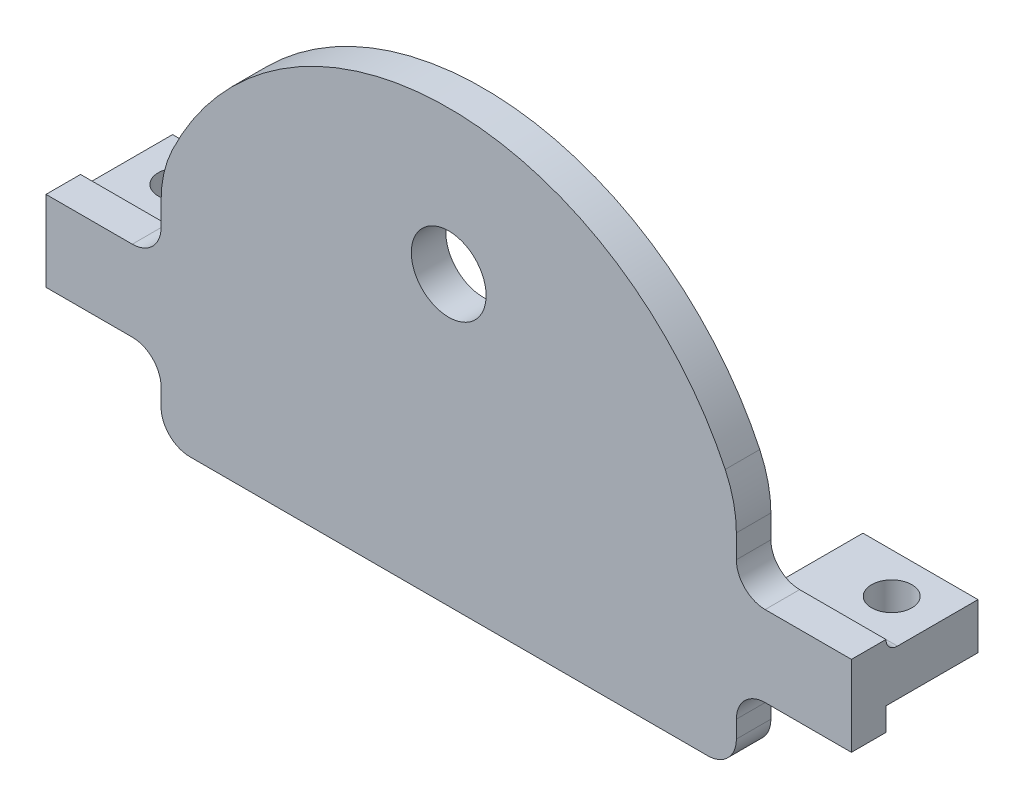
SolidWorks part; units mm, degrees
ref_plane "Front Plane" through (0, 0, 0) normal (0, 0, 1) x (1, 0, 0)
ref_plane "Top Plane" through (0, 0, 0) normal (0, 1, 0) x (1, 0, 0)
ref_plane "Right Plane" through (0, 0, 0) normal (1, 0, 0) x (0, 0, -1)
sketch "Sketch1" plane through (0, 0, 0) normal (0, 0, 1) x (1, 0, 0)
  line L1 (10, 77.5) -> (-10, 77.5)
  line L2 (10, 77.5) -> (10, -77.5)
  line L3 (10, -77.5) -> (-10, -77.5)
  line L4 (-10, 77.5) -> (-10, -77.5)
  line L5 (10, 77.5) -> (-10, -77.5) construction
  line L6 (10, -77.5) -> (-10, 77.5) construction
  point P0 (0, 0)
  dimension "D1" = 20
  dimension "D2" = 155
extrude "Boss-Extrude1" add sketch "Sketch1" along normal blind 4
sketch "Sketch2" plane through (0, 0, 4) normal (0, 0, 1) x (1, 0, 0)
  line L0 (10, -77.5) -> (10, 77.5) construction
  line L1 (-10, -77.5) -> (10, -77.5)
  line L2 (-10, -77.5) -> (-10, -73.5)
  line L3 (-10, -73.5) -> (10, -73.5)
  line L4 (10, -77.5) -> (10, -73.5)
  dimension "D1" = 4
extrude "Boss-Extrude3" add sketch "Sketch2" along normal blind 50 contours L3 L4 L1 L2
sketch "Sketch7" plane through (0, 0, 0) normal (1, 0, 0) x (0, 0, -1)
  line L0 (-29, -73.5) -> (-4, 21.5)
  line L1 (-54, -73.5) -> (-4, -73.5) construction
  line L2 (-4, -73.5) -> (-4, 77.5) construction
  dimension "D1" = 95
  dimension "D2" = 25
rib "Rib2" sketch "Sketch7" sketch "Sketch7" thickness 4 extrusion direction parallel to sketch draft on no parameters "D1"=4
sketch "Sketch8" plane through (0, 0, 4) normal (0, 0, 1) x (1, 0, 0)
  line L0 (-10, 77.5) -> (-10, -73.5) construction
  line L1 (10, 77.5) -> (-10, 77.5)
  line L2 (10, 77.5) -> (10, 74.5)
  line L3 (10, 74.5) -> (-10, 74.5)
  line L4 (-10, 77.5) -> (-10, 74.5)
  dimension "D1" = 3
extrude "Boss-Extrude4" add sketch "Sketch8" along normal blind 3.5
sketch "Sketch9" plane through (0, 0, 7.5) normal (0, 0, 1) x (1, 0, 0)
  line L1 (-35, 79.5) -> (35, 79.5)
  line L2 (-35, 79.5) -> (-35, 74.5)
  line L3 (-35, 74.5) -> (35, 74.5)
  line L4 (35, 79.5) -> (35, 74.5)
  line L5 (10, -73.5) -> (10, 74.5) construction
  line L7 (-10, 74.5) -> (10, 74.5) construction
  dimension "D1" = 70
  dimension "D2" = 25
  dimension "D3" = 5
extrude "Boss-Extrude6" add sketch "Sketch9" along normal blind 3
sketch "Sketch10" plane through (0, 0, 7.5) normal (0, 0, -1) x (-1, 0, 0)
  line L1 (35, 74.5) -> (25, 74.5)
  line L2 (35, 74.5) -> (35, 78.5)
  line L3 (35, 78.5) -> (25, 78.5)
  line L4 (25, 74.5) -> (25, 78.5)
  line L5 (-35, 74.5) -> (-25, 74.5)
  line L6 (-35, 74.5) -> (-35, 78.5)
  line L7 (-35, 78.5) -> (-25, 78.5)
  line L8 (-25, 74.5) -> (-25, 78.5)
  dimension "D1" = 10
  dimension "D2" = 4
extrude "Boss-Extrude7" add sketch "Sketch10" along normal blind 8
sketch "Sketch12" plane through (0, 78.5, 0) normal (0, 1, 0) x (1, 0, 0)
  line L1 (-35, -7.5) -> (-25, -7.5) construction
  line L2 (-35, 0.5) -> (-35, -7.5) construction
  line L3 (35, -7.5) -> (-35, -7.5) construction
  line L4 (35, 0.5) -> (35, -7.5) construction
  circle A0 centre (-31, -3) radius 1.75
  circle A1 centre (31, -3) radius 1.75
  dimension "D1" = 3.5
  dimension "D4" = 3.5
  dimension "D2" = 4.5
  dimension "D3" = 4
  dimension "D5" = 4.5
  dimension "D6" = 4
extrude "Cut-Extrude1" cut sketch "Sketch12" against normal blind 10
sketch "Sketch13" plane through (0, -77.5, 0) normal (0, -1, 0) x (1, 0, 0)
  line L1 (58.3124, -29.3972) -> (-53.0067, -29.3972)
  line L2 (58.3124, -29.3972) -> (58.3124, 70.3466)
  line L3 (58.3124, 70.3466) -> (-53.0067, 70.3466)
  line L4 (-53.0067, -29.3972) -> (-53.0067, 70.3466)
extrude "Cut-Extrude2" cut sketch "Sketch13" against normal up to surface (152 mm away) up to face at (-31, 74.5, 4.75)
sketch "Sketch14" plane through (0, 79.5, 0) normal (0, 1, 0) x (1, 0, 0)
  line L0 (35, -10.5) -> (-35, -10.5) construction
  line L1 (-25, -10.5) -> (25, -10.5)
  line L2 (-25, -10.5) -> (-25, -7.5)
  line L3 (-25, -7.5) -> (25, -7.5)
  line L4 (25, -10.5) -> (25, -7.5)
  line L5 (-25, 0.5) -> (-25, -7.5) construction
  line L6 (25, 0.5) -> (25, -7.5) construction
extrude "Boss-Extrude8" add sketch "Sketch14" along normal blind 6.5
ref_plane "Plane1" through (0, 76, 0) normal (0, -1, 0) x (-1, 0, 0)
mirror "Mirror1" about plane through (0, 76, 0) normal (0, -1, 0) of "Boss-Extrude6", "Boss-Extrude8"
fillet "Fillet1" radius 1 7 edges at (30, 78.5, 7.5) (-30, 78.5, 7.5) (10, 76, 7.5) (-10, 76, 7.5) (0, 77.5, 7.5) (25, 76.5, 7.5) (-25, 76.5, 7.5)
fillet "Fillet2" radius 2.5 6 edges at (-25, 66, 9) (25, 66, 9) (-25, 72.5, 9) (-25, 79.5, 9) (25, 72.5, 9) (25, 79.5, 9)
sketch "Sketch15" plane through (0, 0, 7.5) normal (0, 0, -1) x (-1, 0, 0)
  line L0 (0, 86) -> (0, 91.001) construction
  line L1 (-25, 86) -> (25, 86) construction
  line L2 (0, 78.5) -> (0, 91.001) construction
  line L3 (-11, 78.5) -> (11, 78.5) construction
  line L4 (0, 91.001) -> (0, 103.502) construction
  line L8 (25, 86) -> (-25, 86)
  arc A0 (-25, 86) -> (25, 86) centre (0, 76.8959) cw
  circle A1 centre (0, 91.001) radius 3.25
  dimension "D1" = 6.5
  dimension "D2" = 5.001
extrude "Boss-Extrude9" add sketch "Sketch15" against normal up to surface (3 mm away) up to face at (0, 75.1091, 10.5)
fillet "Fillet3" radius 10 2 edges at (25, 86, 9) (-25, 86, 9)
